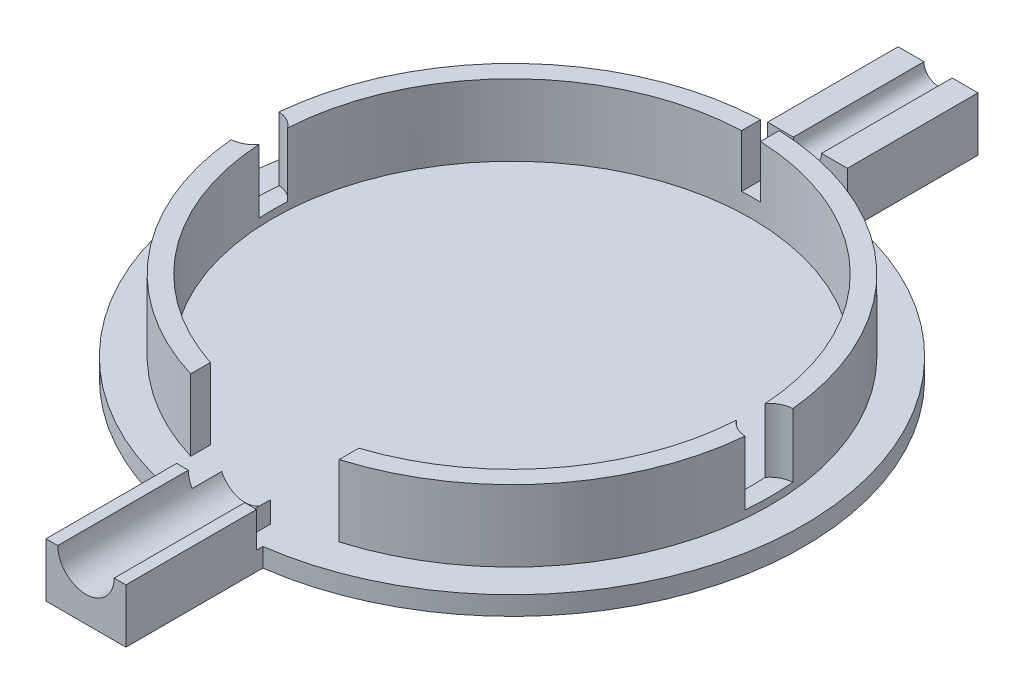
SolidWorks part; units mm, degrees
ref_plane "Front Plane" through (0, 0, 0) normal (0, 0, 1) x (1, 0, 0)
ref_plane "Top Plane" through (0, 0, 0) normal (0, 1, 0) x (1, 0, 0)
ref_plane "Right Plane" through (0, 0, 0) normal (1, 0, 0) x (0, 0, -1)
sketch "Sketch1" plane through (0, 0, 0) normal (0, 1, 0) x (1, 0, 0)
  circle A0 centre (0, 0) radius 31.06
  dimension "D1" = 62.12
extrude "Boss-Extrude1" add sketch "Sketch1" along normal blind 2
sketch "Sketch2" plane through (0, 2, 0) normal (0, 1, 0) x (1, 0, 0)
  circle A0 centre (0, 0) radius 27.46
  circle A1 centre (0, 0) radius 25.46
  circle A2 centre (0, 0) radius 31.06 construction
  dimension "D1" = 2
  dimension "D2" = 3.6
extrude "Boss-Extrude2" add sketch "Sketch2" along normal blind 7.6
sketch "Sketch4" plane through (0, 9.6, 0) normal (0, 1, 0) x (1, 0, 0)
  arc A0 (25.4144, -1.5226) -> (27.3416, -2.5472) centre (27.46, 0) ccw
  circle A1 centre (0, 0) radius 27.46 construction
  arc A2 (-27.3416, -2.5472) -> (-25.4144, -1.5226) centre (-27.46, 0) ccw
  circle A3 centre (0, 0) radius 25.46 construction
  arc A4 (-25.4144, 1.5226) -> (-25.4144, -1.5226) centre (0, 0) ccw
  arc A5 (-27.3416, 2.5472) -> (-27.3416, -2.5472) centre (0, 0) ccw
  arc A6 (25.4144, -1.5226) -> (25.4144, 1.5226) centre (0, 0) ccw
  arc A7 (27.3416, -2.5472) -> (27.3416, 2.5472) centre (0, 0) ccw
  arc A8 (-25.4144, 1.5226) -> (-27.3416, 2.5472) centre (-27.46, 0) ccw
  arc A9 (27.3416, 2.5472) -> (25.4144, 1.5226) centre (27.46, 0) ccw
  circle M1 centre (0, 0) radius 27.46
  circle M2 centre (0, 0) radius 25.46
  dimension "D1" = 5.1
  dimension "D2" = 5.1
extrude "Cut-Extrude1" cut sketch "Sketch4" against normal blind 6.8 contours A9 A0 M1 M2 | A4 A2 A5 A8 region at (26.5014, 9.6, 0)
sketch "Sketch5" plane through (0, 9.6, 0) normal (0, 1, 0) x (1, 0, 0)
  line L0 (0, -25.46) -> (0, -27.46)
  line L1 (3, -25.2826) -> (3, -27.2956)
  line L2 (-3, -25.2826) -> (-3, -27.2956)
  line L3 (3, -25.46) -> (3, -27.46) construction
  line L4 (-3, -25.46) -> (-3, -27.46) construction
  arc A0 (-25.4144, -1.5226) -> (25.4144, -1.5226) centre (0, 0) ccw construction
  arc A1 (-27.3416, -2.5472) -> (27.3416, -2.5472) centre (0, 0) ccw construction
  arc A3 (-3, -25.2826) -> (3, -25.2826) centre (0, 0) ccw
  arc A4 (-3, -27.2956) -> (3, -27.2956) centre (0, 0) ccw
  arc M2 (-27.3416, -2.5472) -> (27.3416, -2.5472) centre (0, 0) ccw
  arc M4 (25.4144, -1.5226) -> (-25.4144, -1.5226) centre (0, 0) cw
  dimension "D1" = 3
  dimension "D2" = 3
extrude "Cut-Extrude2" cut sketch "Sketch5" against normal blind 6.8 contours L2 L0 M4 M2 | L1 L0 M4 M2 region at (1.5016, 9.6, 26.403) region at (-1.5016, 9.6, 26.403)
sketch "Sketch7" plane through (0, 2, 0) normal (0, 1, 0) x (1, 0, 0)
  line L2 (2.6, -28.3014) -> (2.6, -30.951)
  line L3 (-2.6, -28.3014) -> (-2.6, -30.951)
  line L4 (3, -25.2826) -> (3, -27.2956) construction
  circle A0 centre (0, 0) radius 31.06 construction
  arc A1 (-2.6, -30.951) -> (2.6, -30.951) centre (0, 0) ccw
  arc A4 (-2.6, -28.3014) -> (2.6, -28.3014) centre (0, 0.0395) ccw
  dimension "D1" = 5.2
  dimension "D2" = 0.4
extrude "Boss-Extrude5" add sketch "Sketch7" along normal blind 7.6
ref_plane "Plane1" through (0, 0, 31.06) normal (0, 0, 1) x (1, 0, 0)
sketch "Sketch8" plane through (0, 0, 31.06) normal (0, 0, 1) x (1, 0, 0)
  line L0 (2.6, 9.6) -> (-2.6, 9.6) construction
  line L1 (2.6, 9.6) -> (-2.6, 9.6)
  line L2 (31.06, 2) -> (-31.06, 2) construction
  line L3 (2.6, 2) -> (-2.6, 2)
  line L4 (2.6, 9.6) -> (2.6, 2) construction
  line L5 (2.6, 9.6) -> (2.6, 2)
  line L6 (-2.6, 9.6) -> (-2.6, 2) construction
  line L7 (-2.6, 9.6) -> (-2.6, 2)
  line L8 (-2.6, 5.75) -> (2.6, 5.75)
  circle A0 centre (0, 5.75) radius 3
  dimension "D2" = 6
  dimension "D1" = 3.75
extrude "Cut-Extrude3" cut sketch "Sketch8" against normal blind 7.6 contours L7 A0 L5 L8 | L5 A0 L7 L8 | A0 L5 L1 L7 region at (0, 8.8875, 31.06) region at (0, 7.0662, 31.06) region at (0, 4.4338, 31.06)
sketch "Sketch9" plane through (0, 0, 0) normal (0, 0, 1) x (1, 0, 0)
  line L0 (25.4144, 9.6) -> (-25.4144, 9.6) construction
  line L1 (-1, 4) -> (1, 4)
  line L2 (-1, 4) -> (-1, 9.6)
  line L3 (-1, 6) -> (1, 6)
  line L4 (1, 4) -> (1, 9.6)
  line L5 (-1, 4) -> (1, 6) construction
  line L6 (-1, 6) -> (1, 4) construction
  line L7 (1, 9.6) -> (-1, 9.6)
  point P0 (0, 5)
  dimension "D1" = 5
  dimension "D2" = 2
  dimension "D3" = 2
extrude "Cut-Extrude4" cut sketch "Sketch9" against normal through all contours L1 L4 L3 L2 | L4 L7 L2 L3 region at (0, 5, 0) region at (0, 7.8, 0)
sketch "Sketch11" plane through (0, 9.6, 0) normal (0, 1, 0) x (1, 0, 0)
  line L2 (-7.9, -27.9874) -> (7.9, -27.9874)
  line L4 (7.9, -24.1658) -> (-7.9, -24.1658)
  line L5 (7.9, -24.1658) -> (7.9, -28.7542)
  line L6 (7.9, -28.7542) -> (-7.9, -28.7542)
  line L7 (-7.9, -24.1658) -> (-7.9, -28.7542)
  line L8 (7.9, -24.1658) -> (-7.9, -28.7542) construction
  line L9 (7.9, -28.7542) -> (-7.9, -24.1658) construction
  arc A2 (3, -25.2826) -> (25.4144, -1.5226) centre (0, 0) ccw construction
  arc A3 (3, -25.2826) -> (25.4144, -1.5226) centre (0, 0) ccw
  point P7 (0, -26.46)
  line M1 (-3, -27.2956) -> (-3, -25.2826)
  arc M2 (-3, -25.2826) -> (-25.4144, -1.5226) centre (0, 0) cw
  arc M4 (-27.3416, -2.5472) -> (-3, -27.2956) centre (0, 0) ccw
  dimension "D1" = 15.8
extrude "Cut-Extrude5" cut sketch "Sketch11" against normal up to surface (7.6 mm away) contours A3 | L4 L7 L2 L5 M2 M1 M4 | L7 M2 M4 M1 region at (1.0892, 9.6, 26.1222) region at (-5.4664, 9.6, 25.8478) up to face at (0, 2, 27.46)
sketch "Sketch12" plane through (0, 0, 0) normal (0, -1, 0) x (1, 0, 0)
  line L0 (0, 31.06) -> (0, 45.35)
  line L1 (-4.25, 31.06) -> (4.25, 31.06)
  line L2 (4.25, 30.7679) -> (4.25, 45.35)
  line L3 (-4.25, 30.7679) -> (-4.25, 45.35)
  line L4 (-4.25, 45.35) -> (4.25, 45.35)
  line L5 (5.5481, 0) -> (-4.25, 0)
  line L6 (-14.4841, 45.35) -> (8.5, 45.35) construction
  line L7 (-14.4841, 31.06) -> (8.5, 31.06) construction
  line L8 (-4.25, -45.35) -> (4.25, -45.35)
  line L9 (-4.25, -30.7679) -> (-4.25, -45.35)
  line L10 (4.25, -30.7679) -> (4.25, -45.35)
  line L11 (-4.25, -31.06) -> (4.25, -31.06)
  line L12 (0, -31.06) -> (0, -45.35)
  circle A0 centre (0, 0) radius 31.06 construction
  circle A1 centre (0, 0) radius 31.06
  point P6 (4.25, 0)
  point P8 (-4.25, 0)
  circle M1 centre (0, 0) radius 31.06
  dimension "D1" = 14.29
  dimension "D5" = 14.29
extrude "Boss-Extrude7" add sketch "Sketch12" against normal blind 2 contours L4 L0 L1 L2 | L4 L3 L1 L0 | L2 L1 M1 | L3 L1 M1 | L11 L12 L8 L10 | L12 L11 L9 L8 | L9 L11 M1 | L11 L10 M1 region at (-2.125, 0, 38.205) region at (-3.1885, 0, 30.9724) region at (2.125, 0, 38.205) region at (3.1885, 0, 30.9724) region at (-3.1885, 0, -30.9724) region at (3.1885, 0, -30.9724) region at (-2.125, 0, -38.205) region at (2.125, 0, -38.205)
sketch "Sketch13" plane through (0, 0, 45.35) normal (0, 0, 1) x (1, 0, 0)
  line L0 (-4.25, 2) -> (4.25, 2) construction
  line L1 (-4.25, 2) -> (4.25, 2)
  line L2 (-3, 5.75) -> (-4.25, 5.75)
  line L3 (4.25, 2) -> (-4.25, 2)
  line L4 (4.25, 2) -> (4.25, 5.75)
  line L5 (4.25, 5.75) -> (3, 5.75)
  line L6 (-4.25, 2) -> (-4.25, 5.75)
  arc A0 (-3, 5.75) -> (3, 5.75) centre (0, 5.75) ccw
  dimension "D2" = 6
  dimension "D1" = 3.75
extrude "Boss-Extrude8" add sketch "Sketch13" against normal blind 13.9 contours L3 L6 L2 A0 L5 L4
sketch "Sketch14" plane through (0, 0, 31.06) normal (0, 0, 1) x (1, 0, 0)
  line L3 (-2.6, 2) -> (2.6, 2)
  line L4 (2.6, 2) -> (2.6, 4.2533)
  line L5 (-2.6, 4.2533) -> (-2.6, 2)
  line L6 (-2.6, 2) -> (2.6, 2)
  line L7 (2.6, 2) -> (2.6, 4.2533)
  line L8 (-2.6, 4.2533) -> (-2.6, 2)
  arc A1 (-2.6, 4.2533) -> (2.6, 4.2533) centre (0, 5.75) ccw
  arc A2 (-2.6, 4.2533) -> (2.6, 4.2533) centre (0, 5.75) ccw
  dimension "D1" = 0
extrude "Boss-Extrude9" add sketch "Sketch14" along normal blind 2 and the other way blind 2
sketch "Sketch15" plane through (0, 0, -45.35) normal (0, 0, -1) x (-1, 0, 0)
  line L0 (-1.5, 5.75) -> (-4.25, 5.75)
  line L1 (4.25, 0) -> (-4.25, 0)
  line L2 (4.25, 0) -> (4.25, 5.75)
  line L3 (4.25, 5.75) -> (1.5, 5.75)
  line L4 (-4.25, 0) -> (-4.25, 5.75)
  arc A0 (-1.5, 5.75) -> (1.5, 5.75) centre (0, 5.75) ccw
  dimension "D2" = 3
  dimension "D1" = 5.75
extrude "Boss-Extrude10" add sketch "Sketch15" against normal blind 13.9
